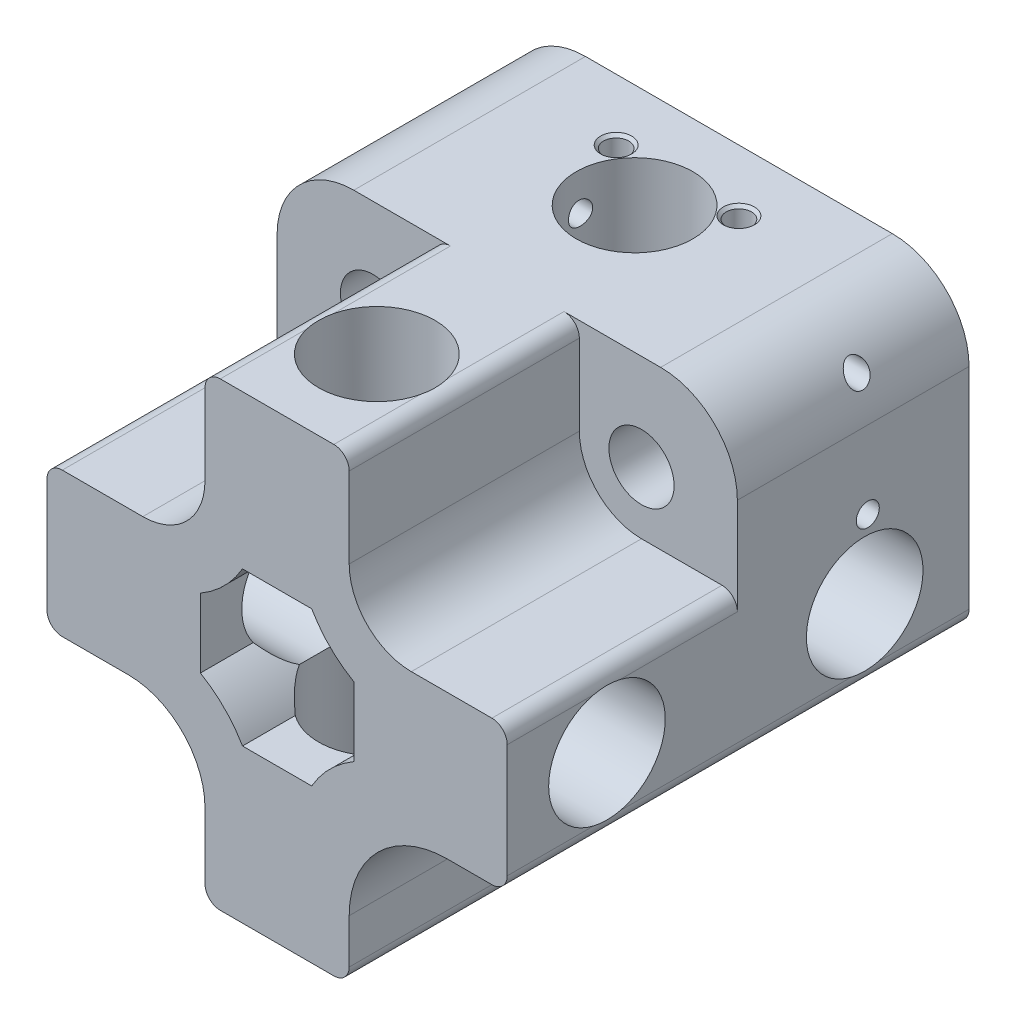
SolidWorks part; units mm, degrees
note: '?' marks a value the reader was unsure of.
material "Lega 1060"
ref_plane "Piano frontale" through (0, 0, 0) normal (0, 0, 1) x (1, 0, 0)
ref_plane "Piano superiore" through (0, 0, 0) normal (0, 1, 0) x (1, 0, 0)
ref_plane "Piano destro" through (0, 0, 0) normal (1, 0, 0) x (0, 0, -1)
sketch "Schizzo1" plane through (0, 0, 0) normal (0, 0, 1) x (1, 0, 0)
  line L0 (-60, 0) -> (-60, 60)
  line L1 (-60, 60) -> (0, 60)
  line L6 (0, 0) -> (0, 60)
  line L7 (0, 0) -> (-60, 0)
  point P0 (0, 0)
  dimension "D1" = 60
extrude "Estrusione-Estrusione1" add sketch "Schizzo1" along normal blind 60.2
sketch "Schizzo2" plane through (0, 0, 0) normal (1, 0, 0) x (0, 0, -1)
  line L2 (-13.6, 30) -> (-47.2, 30) construction
  line L3 (-60.2, 0) -> (0, 0) construction
  line L4 (-60.2, 60) -> (0, 60) construction
  line L5 (-54.8, 30) -> (-60.2, 30) construction
  line L8 (-60.2, 0) -> (-60.2, 60) construction
  circle A0 centre (-13.6, 30) radius 7.6
  circle A1 centre (-47.2, 30) radius 7.6
  dimension "D1" = 15.2
  dimension "D3" = 15.2
  dimension "D2" = 33.6
  dimension "D5" = 13
extrude "Taglio-Estrusione1" cut sketch "Schizzo2" against normal through all
sketch "Schizzo3" plane through (0, 60, 0) normal (0, 1, 0) x (0, 0, -1)
  line L0 (-47.2, 30) -> (-13.6, 30) construction
  line L3 (-60.2, 0) -> (0, 0) construction
  line L7 (-60.2, 60) -> (0, 60) construction
  line L8 (-60.2, 0) -> (-60.2, 60) construction
  circle A0 centre (-47.2, 30) radius 7.6
  circle A1 centre (-13.6, 30) radius 7.6
  dimension "D1" = 15.2
  dimension "D4" = 15.2
  dimension "D2" = 13
  dimension "D3" = 33.6
extrude "Taglio-Estrusione2" cut sketch "Schizzo3" against normal through all from surface at 0 starting at face at (-30, 60, 30.1)
sketch "Schizzo4" plane through (0, 0, 60.2) normal (0, 0, 1) x (1, 0, 0)
  line L0 (11.7083, 30) -> (-30, 30) construction
  line L1 (-30, 30) -> (-30, 11.0363) construction
  line L2 (0, 0) -> (0, 60) construction
  line L3 (-60, 60) -> (-60, 0) construction
  line L4 (-60, 0) -> (0, 0) construction
  line L5 (0, 60) -> (-60, 60) construction
  circle A0 centre (-12.5, 12.5) radius 8.1
  circle A1 centre (-47.5, 12.5) radius 8.1
  circle A2 centre (-47.5, 47.5) radius 8.1
  circle A3 centre (-12.5, 47.5) radius 8.1
  point P22 (-30, 30)
  dimension "D1" = 16.2
  dimension "D3" = 12.5
  dimension "D4" = 12.5
  dimension "D2" = 4
extrude "Taglio-Estrusione3" cut sketch "Schizzo4" against normal through all
ref_plane "Piano3" through (0, 30, 0) normal (0, -1, 0) x (-1, 0, 0)
sketch "Schizzo7" plane through (0, 0, 60.2) normal (0, 0, 1) x (1, 0, 0)
  line L0 (-60, 60) -> (-30, 30) construction
  line L1 (-30, 30) -> (-60, 0) construction
  line L2 (-20, 34.5096) -> (-20, 25.4904)
  line L3 (0, 60) -> (-60, 60) construction
  line L4 (-25.4904, 20) -> (-34.5096, 20)
  line L5 (-40, 25.4904) -> (-40, 34.5096)
  line L6 (-34.5096, 40) -> (-25.4904, 40)
  arc A0 (-20, 34.5096) -> (-25.4904, 40) centre (-12.5, 47.5) cw
  arc A1 (-20, 25.4904) -> (-25.4904, 20) centre (-12.5, 12.5) ccw
  arc A2 (-34.5096, 20) -> (-40, 25.4904) centre (-47.5, 12.5) ccw
  arc A3 (-34.5096, 40) -> (-40, 34.5096) centre (-47.5, 47.5) cw
  circle A4 centre (-12.5, 47.5) radius 8.1 construction
  circle A5 centre (-12.5, 47.5) radius 8.1 construction
  circle A6 centre (-47.5, 47.5) radius 8.1 construction
  circle A7 centre (-47.5, 47.5) radius 8.1 construction
  circle A8 centre (-47.5, 12.5) radius 8.1 construction
  circle A9 centre (-47.5, 12.5) radius 8.1 construction
  circle A13 centre (-12.5, 12.5) radius 8.1 construction
  circle A14 centre (-12.5, 12.5) radius 8.1 construction
  dimension "D1" = 20
  dimension "D2" = 15
extrude "Taglio-Estrusione4" cut sketch "Schizzo7" against normal through all
fillet "Raccordo1" radius 10 4 edges at (-60, 60, 30.1) (-60, 0, 30.1) (0, 60, 30.1) (0, 0, 30.1)
sketch "Schizzo8" plane through (0, 0, 60.2) normal (0, 0, 1) x (1, 0, 0)
  line L0 (-47.5, 20.6) -> (-58, 20.6)
  line L1 (-60, 50) -> (-60, 10) construction
  line L2 (-39.4, 12.5) -> (-39.4, 2)
  line L3 (-34.3179, 30) -> (-30, 30) construction
  line L4 (-60, 22.6) -> (-60, 10)
  line L5 (-50, 0) -> (-37.4, 0)
  line L6 (-30, 30) -> (-30, 35.3582) construction
  line L7 (0, 10) -> (0, 50) construction
  line L8 (-50, 0) -> (-10, 0) construction
  line L9 (-10, 60) -> (-50, 60) construction
  line L10 (-39.4, 47.5) -> (-39.4, 58)
  line L11 (-47.5, 39.4) -> (-58, 39.4)
  line L12 (-37.4, 60) -> (-50, 60)
  line L13 (-60, 50) -> (-60, 37.4)
  line L14 (-30, 30) -> (-24.6418, 30) construction
  line L15 (-12.5, 39.4) -> (-2, 39.4)
  line L16 (-20.6, 47.5) -> (-20.6, 58)
  line L17 (0, 37.4) -> (0, 50)
  line L18 (-10, 60) -> (-22.6, 60)
  line L19 (-30, 30) -> (-30, 24.6418) construction
  line L20 (-20.6, 12.5) -> (-20.6, 2)
  line L21 (-12.5, 20.6) -> (-2, 20.6)
  line L22 (-22.6, 0) -> (-10, 0)
  line L23 (0, 10) -> (0, 22.6)
  line L24 (-30, 30) -> (-35.3582, 30) construction
  line L25 (-39.4, 47.5) -> (-39.4, 58) [skipped]
  line L26 (-37.4, 60) -> (-50, 60) [skipped]
  line L27 (-60, 50) -> (-60, 37.4) [skipped]
  line L28 (-47.5, 39.4) -> (-58, 39.4) [skipped]
  line L29 (-12.5, 39.4) -> (-2, 39.4) [skipped]
  line L30 (0, 37.4) -> (0, 50) [skipped]
  line L31 (-10, 60) -> (-22.6, 60) [skipped]
  line L32 (-20.6, 47.5) -> (-20.6, 58) [skipped]
  line L33 (-20.6, 12.5) -> (-20.6, 2) [skipped]
  line L34 (-22.6, 0) -> (-10, 0) [skipped]
  line L35 (0, 10) -> (0, 22.6) [skipped]
  line L36 (-12.5, 20.6) -> (-2, 20.6) [skipped]
  arc A0 (-47.5, 20.6) -> (-39.4, 12.5) centre (-47.5, 12.5) cw
  circle A1 centre (-47.5, 12.5) radius 8.1 construction
  arc A2 (-39.4, 2) -> (-37.4, 0) centre (-37.4, 2) ccw
  arc A3 (-58, 20.6) -> (-60, 22.6) centre (-58, 22.6) cw
  arc A4 (-60, 10) -> (-50, 0) centre (-50, 10) ccw
  arc A5 (-60, 10) -> (-50, 0) centre (-50, 10) ccw construction
  arc A6 (-39.4, 47.5) -> (-47.5, 39.4) centre (-47.5, 47.5) cw
  arc A7 (-58, 39.4) -> (-60, 37.4) centre (-58, 37.4) ccw
  arc A8 (-39.4, 58) -> (-37.4, 60) centre (-37.4, 58) cw
  arc A9 (-50, 60) -> (-60, 50) centre (-50, 50) ccw
  arc A10 (-12.5, 39.4) -> (-20.6, 47.5) centre (-12.5, 47.5) cw
  arc A11 (-20.6, 58) -> (-22.6, 60) centre (-22.6, 58) ccw
  arc A12 (-2, 39.4) -> (0, 37.4) centre (-2, 37.4) cw
  arc A13 (0, 50) -> (-10, 60) centre (-10, 50) ccw
  arc A14 (-20.6, 12.5) -> (-12.5, 20.6) centre (-12.5, 12.5) cw
  arc A15 (-2, 20.6) -> (0, 22.6) centre (-2, 22.6) ccw
  arc A16 (-20.6, 2) -> (-22.6, 0) centre (-22.6, 2) cw
  arc A17 (-10, 0) -> (0, 10) centre (-10, 10) ccw
  arc A18 (-39.4, 58) -> (-37.4, 60) centre (-37.4, 58) cw [skipped]
  arc A19 (-50, 60) -> (-60, 50) centre (-50, 50) ccw [skipped]
  arc A20 (-58, 39.4) -> (-60, 37.4) centre (-58, 37.4) ccw [skipped]
  arc A21 (-2, 39.4) -> (0, 37.4) centre (-2, 37.4) cw [skipped]
  arc A22 (0, 50) -> (-10, 60) centre (-10, 50) ccw [skipped]
  arc A23 (-20.6, 58) -> (-22.6, 60) centre (-22.6, 58) ccw [skipped]
  arc A24 (-20.6, 2) -> (-22.6, 0) centre (-22.6, 2) cw [skipped]
  arc A25 (-10, 0) -> (0, 10) centre (-10, 10) ccw [skipped]
  arc A26 (-2, 20.6) -> (0, 22.6) centre (-2, 22.6) ccw [skipped]
  point P67 (-30, 30)
  point P122 (-30, 30)
  dimension "D1" = 2
  dimension "D2" = 4
  dimension "D3" = 4
extrude "Taglio-Estrusione5" cut sketch "Schizzo8" against normal blind 30
sketch "Schizzo10" plane through (0, 0, 30.2) normal (0, 0, 1) x (1, 0, 0)
  circle A0 centre (-47.5, 47.5) radius 8.1
  circle A5 centre (-12.5, 47.5) radius 8.1
  arc A6 (-12.5, 39.4) -> (-20.6, 47.5) centre (-12.5, 47.5) ccw construction
  arc A7 (-39.4, 47.5) -> (-47.5, 39.4) centre (-47.5, 47.5) ccw construction
extrude "Estrusione-Estrusione3" add sketch "Schizzo10" against normal blind 10
sketch "Schizzo13" plane through (0, 0, 30.2) normal (0, 0, 1) x (1, 0, 0)
  circle A0 centre (-12.5, 47.5) radius 4.25
  circle A1 centre (-47.5, 47.5) radius 4.25
  circle A4 centre (-12.5, 47.5) radius 8.1 construction
  circle A5 centre (-47.5, 47.5) radius 8.1 construction
  dimension "D1" = 8.5
extrude "Taglio-Estrusione6" cut sketch "Schizzo13" against normal blind 9.8
ref_plane "Piano4" through (-30, 0, 0) normal (-1, 0, 0) x (0, 0, 1)
ref_plane "Piano5" through (0, 30, 0) normal (0, -1, 0) x (-1, 0, 0)
ref_axis "Assi1" through (-30, 30, 16.664) along (0, 0, 1)?
sketch "Schizzo14" plane through (0, 0, 30.2) normal (0, 0, 1) x (1, 0, 0)
  line L0 (-20.6, 12.5) -> (-20.6, 2) construction
  line L1 (-22.6, 0) -> (-10, 0) construction
  line L2 (0, 10) -> (0, 22.6) construction
  line L3 (-2, 20.6) -> (-12.5, 20.6) construction
  line L4 (-47.5, 20.6) -> (-58, 20.6)
  line L5 (-60, 22.6) -> (-60, 10)
  line L6 (-50, 0) -> (-37.4, 0)
  line L7 (-39.4, 2) -> (-39.4, 12.5)
  line L8 (-47.5, 20.6) -> (-58, 20.6)
  line L9 (-60, 22.6) -> (-60, 10)
  line L10 (-50, 0) -> (-37.4, 0)
  line L11 (-39.4, 2) -> (-39.4, 12.5)
  line L12 (-20.6, 12.5) -> (-20.6, 2)
  line L13 (-22.6, 0) -> (-10, 0)
  line L14 (0, 10) -> (0, 22.6)
  line L15 (-2, 20.6) -> (-12.5, 20.6)
  arc A0 (-39.4, 12.5) -> (-47.5, 20.6) centre (-47.5, 12.5) ccw construction
  arc A2 (-39.4, 12.5) -> (-47.5, 20.6) centre (-47.5, 12.5) ccw
  arc A4 (-47.5, 20.6) -> (-39.4, 12.5) centre (-47.5, 12.5) ccw
  arc A5 (-60, 22.6) -> (-58, 20.6) centre (-58, 22.6) ccw
  arc A6 (-60, 10) -> (-50, 0) centre (-50, 10) ccw
  arc A7 (-39.4, 2) -> (-37.4, 0) centre (-37.4, 2) ccw
  arc A8 (-47.5, 20.6) -> (-39.4, 12.5) centre (-47.5, 12.5) ccw
  arc A9 (-60, 22.6) -> (-58, 20.6) centre (-58, 22.6) ccw
  arc A10 (-60, 10) -> (-50, 0) centre (-50, 10) ccw
  arc A11 (-39.4, 2) -> (-37.4, 0) centre (-37.4, 2) ccw
  arc A12 (-39.4, 12.5) -> (-47.5, 20.6) centre (-47.5, 12.5) ccw
  arc A13 (-10, 0) -> (0, 10) centre (-10, 10) ccw construction
  arc A14 (-22.6, 0) -> (-20.6, 2) centre (-22.6, 2) ccw construction
  arc A15 (-2, 20.6) -> (0, 22.6) centre (-2, 22.6) ccw construction
  arc A17 (-10, 0) -> (0, 10) centre (-10, 10) ccw
  arc A18 (-22.6, 0) -> (-20.6, 2) centre (-22.6, 2) ccw
  arc A19 (-2, 20.6) -> (0, 22.6) centre (-2, 22.6) ccw
  arc A20 (-12.5, 20.6) -> (-20.6, 12.5) centre (-12.5, 12.5) ccw construction
  arc A21 (-12.5, 20.6) -> (-20.6, 12.5) centre (-12.5, 12.5) ccw
  dimension "D1" = 0
extrude "Taglio-Estrusione7" cut sketch "Schizzo14" against normal up to next (30.2 mm away) and the other way up to next (30 mm away) contours L15 A21 L12 A18 L13 A17 L14 A19
sketch "Schizzo15" plane through (0, 0, 60.2) normal (0, 0, 1) x (1, 0, 0)
  line L0 (-25.4982, 25.4982) -> (0, 0) construction
  line L1 (-37.4, 0) -> (-22.6, 0) construction
  line L2 (0, 22.6) -> (0, 37.4) construction
  line L5 (-20.6, 12.5) -> (-20.6, 7.8)
  line L6 (-7.8, 20.6) -> (-12.5, 20.6)
  line L7 (-47.5, 20.6) -> (-58, 20.6) construction
  line L8 (-2, 20.6) -> (-12.5, 20.6) construction
  line L9 (-39.4, 2) -> (-39.4, 12.5) construction
  line L10 (-20.6, 12.5) -> (-20.6, 2) construction
  line L11 (-47.5, 20.6) -> (-58, 20.6) construction
  line L12 (-49.4, 20.6) -> (-47.5, 20.6)
  line L13 (-39.4, 12.5) -> (-39.4, 10.6)
  arc A0 (-7.8, 20.6) -> (-20.6, 7.8) centre (-7.8, 7.8) ccw
  arc A1 (-12.5, 20.6) -> (-20.6, 12.5) centre (-12.5, 12.5) ccw construction
  arc A2 (-12.5, 20.6) -> (-20.6, 12.5) centre (-12.5, 12.5) ccw
  arc A3 (-49.4, 20.6) -> (-39.4, 10.6) centre (-49.4, 10.6) cw
  arc A4 (-39.4, 12.5) -> (-47.5, 20.6) centre (-47.5, 12.5) ccw
  arc A6 (-39.4, 12.5) -> (-47.5, 20.6) centre (-47.5, 12.5) ccw construction
  dimension "D1" = 25.6
  dimension "D2" = 10
extrude "Estrusione-Estrusione4" add sketch "Schizzo15" against normal through all
hole_wizard "Foro Ø2.6 (2.6)-2" positions "Schizzo19" profile "Schizzo18" hole size "Ø2.6" standard "ISO"
sketch "Schizzo19" plane through (0, 0, 0) normal (0, 0, -1) x (-1, 0, 0)
  line L0 (30, 35.2948) -> (30, -6.7357) construction
  line L4 (30, 30) -> (0, 0) construction
  line L7 (2, 20.6) -> (7.8, 20.6) construction
  line L8 (20.6, 7.8) -> (20.6, 2) construction
  line L9 (39.4, 2) -> (39.4, 10.6) construction
  point P0 (24.1, 16.1)
  point P2 (16.1, 24.1)
  point P4 (35.9, 16.1)
  point P6 (43.9, 24.1)
  dimension "D1" = 8
  dimension "D2" = 3.5
sketch "Schizzo18" plane through (-24.1, 16.1, 0) normal (1, 0, 0) x (0, 1, 0)
  line L0 (0, 0) -> (0, 10.7811)
  line L1 (0, 10.7811) -> (1.3, 10)
  line L2 (1.3, 10) -> (1.3, 0)
  line L5 (1.3, 0) -> (0, 0)
  line L10 (0, 10.7811) -> (-1.3, 10) construction
  line L11 (0, -6.35) -> (0, 107.95) construction
  dimension "Hole Dia." = 2.6
  dimension "Hole Depth" = 10
  dimension "Drill Angle" = 118
sketch "Schizzo20" plane through (0, 0, 0) normal (1, 0, 0) x (0, 0, -1)
  line L0 (-20.2, 39.4) -> (-20.2, 55.6) construction
  line L1 (-20.2, 39.4) -> (0, 39.4) construction
  circle A0 centre (-13.2, 39.9) radius 1.5
  dimension "D3" = 3
  dimension "D1" = 7
  dimension "D2" = 0.5
extrude "Taglio-Estrusione8" cut sketch "Schizzo20" against normal blind 71
sketch "Schizzo22" plane through (0, 0, 0) normal (1, 0, 0) x (0, 0, -1)
  line L0 (-20.2, 39.4) -> (-20.2, 55.6) construction
  line L1 (0, 55.6) -> (-20.2, 55.6) construction
  circle A1 centre (-13.2, 55.1) radius 1.5
  dimension "D3" = 3
  dimension "D1" = 7
  dimension "D2" = 0.5
extrude "Taglio-Estrusione9" cut sketch "Schizzo22" against normal blind 71
sketch "Schizzo24" plane through (0, 60, 0) normal (0, 1, 0) x (1, 0, 0)
  line L0 (-30, -16.664) -> (-30, -62.2731) construction
  line L1 (-10, 0) -> (-50, 0) construction
  point P0 (-38, -8)
  point P1 (-22, -8)
  dimension "D1" = 8
  dimension "D2" = 8
  dimension "D3" = 8
  dimension "D4" = 8
hole_wizard "Foro filettato M4x0.7-1" positions "Schizzo26" profile "Schizzo25" tap size "M4x0.7" standard "Ansi Metric"
sketch "Schizzo26" plane through (0, 60, 0) normal (0, 1, 0) x (1, 0, 0)
  point P0 (-38, -8)
  point P3 (-22, -8)
sketch "Schizzo25" plane through (-38, 60, 8) normal (1, 0, 0) x (0, 0, 1)
  line L0 (0, 0) -> (0, 12.4914)
  line L1 (0, 12.4914) -> (1.65, 11.5)
  line L2 (1.65, 11.5) -> (1.65, 0.375)
  line L3 (1.65, 0.375) -> (2.025, 0)
  line L5 (2.025, 0) -> (0, 0)
  line L6 (-1.65, 0.375) -> (-2.025, 0) construction
  line L10 (0, 12.4914) -> (-1.65, 11.5) construction
  line L11 (0, -6.35) -> (0, 107.95) construction
  dimension "Tap Drill Dia." = 3.3
  dimension "Tap Drill Depth" = 11.5
  dimension "Near C'Sink Dia." = 4.05
  dimension "Near C'Sink Angle" = 90
  dimension "Drill Angle" = 118
cosmetic thread "Filettatura del foro1" parameters "D1"=8, "D2"=4
cosmetic thread "Filettatura del foro2" parameters "D1"=8, "D2"=4
